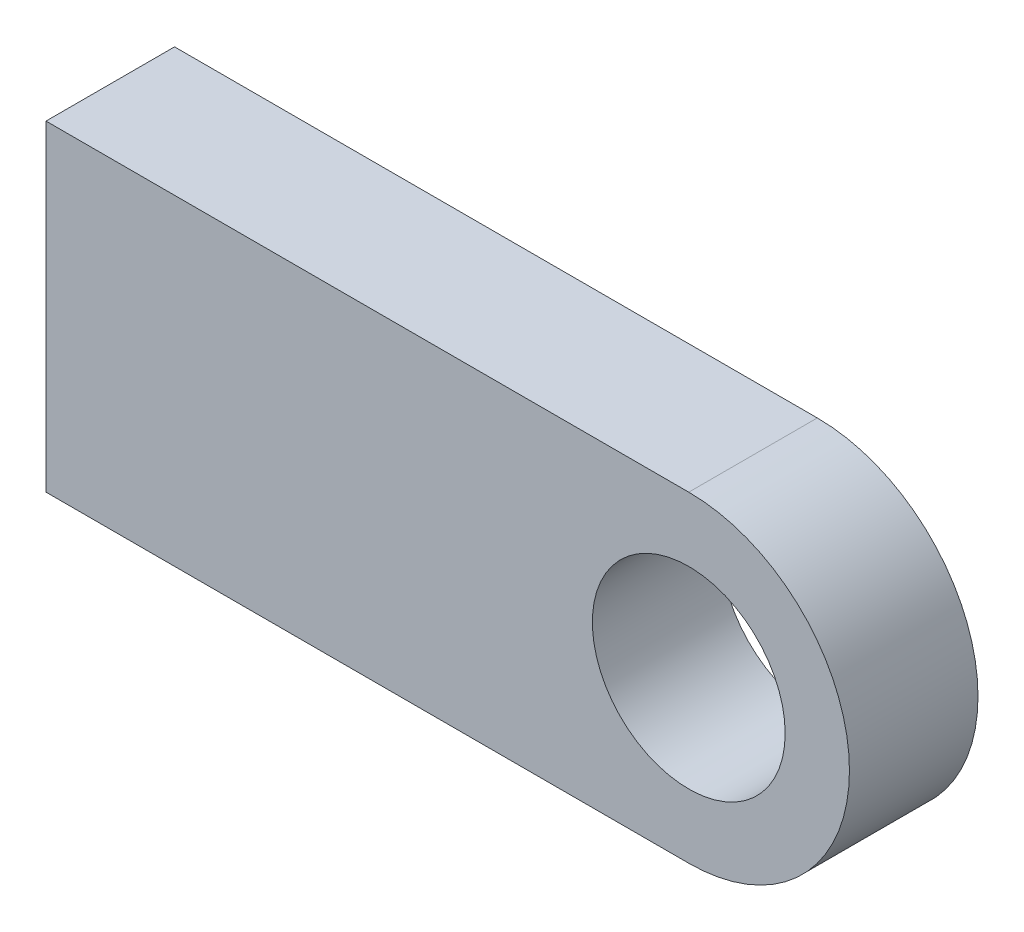
SolidWorks part; units mm, degrees
ref_plane "Front Plane" through (0, 0, 0) normal (0, 0, 1) x (1, 0, 0)
ref_plane "Top Plane" through (0, 0, 0) normal (0, 1, 0) x (1, 0, 0)
ref_plane "Right Plane" through (0, 0, 0) normal (1, 0, 0) x (0, 0, -1)
sketch "Sketch1" plane through (0, 0, 0) normal (0, 0, 1) x (1, 0, 0)
  line L5 (-95, -7.75) -> (5, -7.75)
  line L6 (-95, -7.75) -> (-95, -57.75)
  line L7 (-95, -57.75) -> (5, -57.75)
  arc A0 (5, -7.75) -> (5, -57.75) centre (5, -32.75) cw
  circle A1 centre (5, -32.75) radius 15
  dimension "D3" = 30
  dimension "D1" = 50
  dimension "D2" = 100
extrude "Boss-Extrude1" add sketch "Sketch1" along normal blind 20
